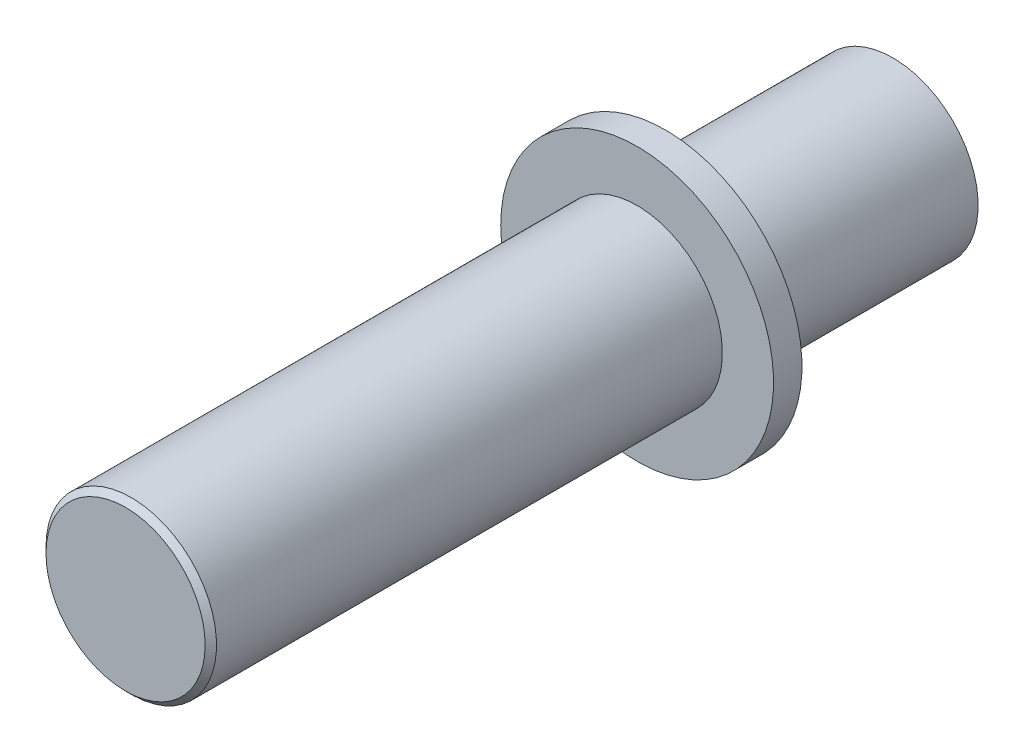
SolidWorks part; units mm, degrees
material "1.0037 (S235JR)"
ref_plane "Front Plane" through (0, 0, 0) normal (0, 0, 1) x (1, 0, 0)
ref_plane "Top Plane" through (0, 0, 0) normal (0, 1, 0) x (1, 0, 0)
ref_plane "Right Plane" through (0, 0, 0) normal (1, 0, 0) x (0, 0, -1)
sketch "Sketch1" plane through (0, 0, 0) normal (0, 0, 1) x (1, 0, 0)
  circle A0 centre (0, 0) radius 15
  dimension "D1" = 30
extrude "Boss-Extrude1" add sketch "Sketch1" along normal blind 90
sketch "Sketch2" plane through (0, 0, 0) normal (0, 0, -1) x (-1, 0, 0)
  circle A0 centre (0, 0) radius 24
  dimension "D1" = 48
extrude "Boss-Extrude2" add sketch "Sketch2" along normal blind 5
chamfer "Chamfer1" distance 1 angle 45 1 edges at (15, 0, 90)
sketch "Sketch4" plane through (0, 0, -5) normal (0, 0, -1) x (-1, 0, 0)
  line L0 (0, 52.6957) -> (0, -55.664) construction
  line L1 (-57.6229, 0) -> (63.7928, 0) construction
  line L2 (0, 0) -> (14.1421, 14.1421) construction
  line L3 (0, 0) -> (-14.1421, -14.1421) construction
  line L4 (0, 0) -> (-14.1421, 14.1421) construction
  line L5 (0, 0) -> (14.1421, -14.1421) construction
  circle A4 centre (0, 0) radius 15
  dimension "D2" = 30
  dimension "D1" = 45
extrude "Boss-Extrude3" add sketch "Sketch4" along normal blind 40
ref_axis "Axis1" through (0, 0, 89) along (0, 0, -1)
ref_point "Point1"
ref_plane "Plane4" through (-15, 0, -45) normal (1, 0, 0) x (0, 0, -1)
sketch "Sketch5" plane through (-15, 0, -45) normal (1, 0, 0) x (0, 0, -1)
  line L0 (-35, 0) -> (-10, 0) construction
  line L3 (8.8509, 0) -> (-44.3447, 0) construction
  line L4 (-134, 0) -> (-45, 0) construction
  line L5 (-35, 3.2841) -> (-10, 3.2841)
  line L6 (-35, -3.2841) -> (-10, -3.2841)
  line L7 (-40, -15) -> (-40, 15) construction
  line L8 (0, -15) -> (0, 15) construction
  arc A0 (-35, 3.2841) -> (-35, -3.2841) centre (-35, 0) ccw
  arc A1 (-10, -3.2841) -> (-10, 3.2841) centre (-10, 0) ccw
  point P2 (-22.5, 0)
  dimension "D3" = 3.2841
  dimension "D1" = 5
  dimension "D2" = 10
  dimension "D4" = 25
extrude "Cut-Extrude1" cut sketch "Sketch5" along normal blind 2
sketch "Sketch6" plane through (0, 0, -45) normal (0, 0, -1) x (-1, 0, 0)
  circle A0 centre (0, 0) radius 8
  dimension "D1" = 16
extrude "Cut-Extrude2" cut sketch "Sketch6" against normal blind 45
